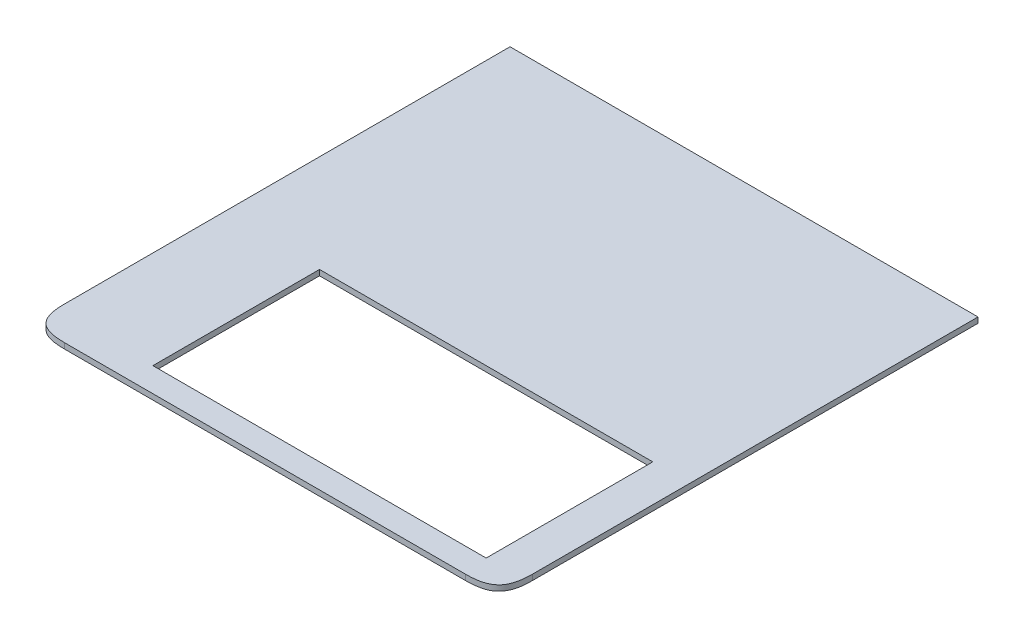
SolidWorks part; units mm, degrees
ref_plane "Front Plane" through (0, 0, 0) normal (0, 0, 1) x (1, 0, 0)
ref_plane "Top Plane" through (0, 0, 0) normal (0, 1, 0) x (1, 0, 0)
ref_plane "Right Plane" through (0, 0, 0) normal (1, 0, 0) x (0, 0, -1)
sketch "Sketch1" plane through (0, 0, 0) normal (0, 1, 0) x (1, 0, 0)
  line L1 (0, 0) -> (337, 0)
  line L2 (0, 0) -> (0, 344.97)
  line L3 (0, 344.97) -> (337, 344.97)
  line L4 (337, 0) -> (337, 344.97)
  line L5 (70.28, 137.5) -> (310.28, 137.5)
  line L6 (70.28, 137.5) -> (70.28, 17.5)
  line L7 (70.28, 17.5) -> (310.28, 17.5)
  line L8 (310.28, 137.5) -> (310.28, 17.5)
  dimension "D1" = 337
  dimension "D2" = 344.97
  dimension "D3" = 240
  dimension "D4" = 120
  dimension "D5" = 17.5
  dimension "D6" = 26.72
extrude "Boss-Extrude1" add sketch "Sketch1" against normal blind 4
fillet "Fillet1" radius 24 2 edges at (0, -2, 0) (337, -2, 0) conic rho 0.55
